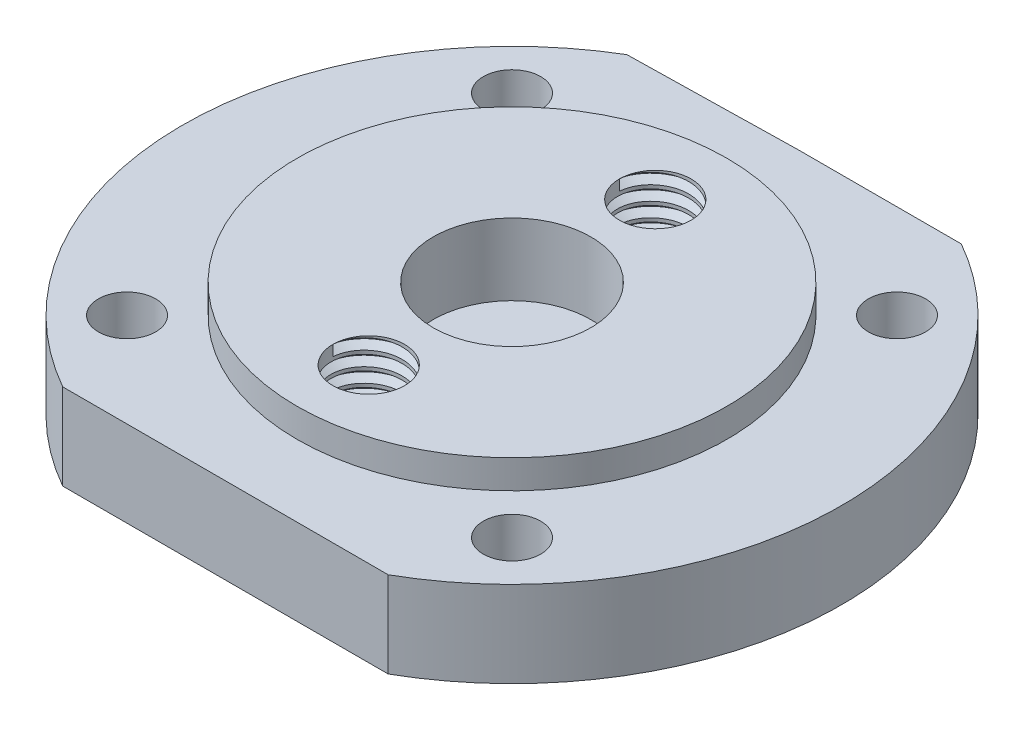
SolidWorks part; units mm, degrees
material "6061 Alloy"
ref_plane "Front Plane" through (0, 0, 0) normal (0, 0, 1) x (1, 0, 0)
ref_plane "Top Plane" through (0, 0, 0) normal (0, 1, 0) x (1, 0, 0)
ref_plane "Right Plane" through (0, 0, 0) normal (1, 0, 0) x (0, 0, -1)
sketch "Sketch1" plane through (0, 0, 0) normal (0, 1, 0) x (1, 0, 0)
  line L0 (0, 0) -> (0, 19.9983)
  line L1 (0, 0) -> (0, -20)
  line L2 (0, 19.9983) -> (11.3608, 19.9983)
  line L3 (0, 19.9983) -> (-11.7567, 19.7681)
  line L4 (0, -20) -> (-11.3578, -20)
  line L5 (0, -20) -> (11.3578, -20)
  circle A0 centre (0, 0) radius 23
  dimension "D1" = 46
  dimension "D2" = 19.9983
  dimension "D3" = 20
extrude "Boss-Extrude1" add sketch "Sketch1" along normal blind 6 contours L3 A0 L4 L1 L0 | L5 A0 L2 L0 L1
sketch "Sketch2" plane through (0, 6, 0) normal (0, 1, 0) x (1, 0, 0)
  line L0 (0, 0) -> (13.435, 13.435)
  line L1 (0, 0) -> (-13.435, -13.435)
  line L2 (13.435, 13.435) -> (-13.435, 13.435)
  line L3 (13.435, 13.435) -> (13.435, -13.435)
  line L4 (13.435, -13.435) -> (-13.435, -13.435)
  line L5 (-13.435, 13.435) -> (-13.435, -13.435)
  circle A0 centre (0, 0) radius 19
  circle A1 centre (-13.435, 13.435) radius 2
  circle A2 centre (13.435, 13.435) radius 2
  circle A3 centre (-13.435, -13.435) radius 2
  circle A4 centre (13.435, -13.435) radius 2
  dimension "D1" = 38
extrude "Cut-Extrude1" cut sketch "Sketch2" against normal through all contours L5 A1 L2 | A0 A1 L5 | L2 A1 A0 | A0 A1 | L4 A3 L1 | L1 A3 L5 | L5 A3 A0 | A0 A3 L4 | A0 A3 | L4 A4 A0 | L3 A4 L4 | A0 A4 L3 | A0 A4 | L0 A2 L3 | L2 A2 L0 | A0 A2 L2 | L3 A2 A0 | A0 A2
sketch "Sketch3" plane through (0, 6, 0) normal (0, 1, 0) x (1, 0, 0)
  circle A0 centre (0, 0) radius 15
extrude "Boss-Extrude2" add sketch "Sketch3" along normal blind 2
sketch "Sketch4" plane through (0, 8, 0) normal (0, 1, 0) x (1, 0, 0)
  circle A0 centre (0, 0) radius 5.5
extrude "Cut-Extrude2" cut sketch "Sketch4" against normal blind 5
sketch "Sketch5" plane through (0, 8, 0) normal (0, 1, 0) x (1, 0, 0)
  point P0 (0, 0)
  point P5 (0, 10)
  point P6 (0, -10)
hole_wizard "M6 Tapped Hole1" positions "Sketch13" profile "Sketch7" tap size "M6" standard "ISO" end condition through all
sketch "Sketch13" plane through (0, 8, 0) normal (0, 1, 0) x (1, 0, 0)
  point P0 (0, 10)
  point P3 (0, -10)
sketch "Sketch7" plane through (0, 8, -10) normal (1, 0, 0) x (0, 0, 1)
  line L0 (0, 0) -> (0, 8)
  line L1 (0, 8) -> (2.5, 8)
  line L2 (2.5, 8) -> (2.5, 0)
  line L5 (2.5, 0) -> (0, 0)
  line L11 (0, -6.35) -> (0, 107.95) construction
  dimension "Thru Tap Drill Dia." = 5
  dimension "Thru Tap Drill Depth" = 8
cosmetic thread "Hole Thread1" parameters "D2"=6
cosmetic thread "Hole Thread2" parameters "D2"=6
thread "Thread1" pitch 1 profile "Thread Profile1" start angle 0, offset 0, length 100, pitch 1, diameter 5
ref_plane "Plane1" through (-2.5, 8, -10) normal (0, 0, 1) x (-1, 0, 0)
sketch "Thread Profile1" plane through (-2.5, 8, -10) normal (0, 0, 1) x (-1, 0, 0)
  line L0 (0, 0) -> (0, 1) construction
  line L1 (0, 0) -> (0.5413, 0.3125)
  line L2 (0.5413, 0.3125) -> (0.5413, 0.4375)
  line L3 (0.5413, 0.4375) -> (0, 0.75)
  line L4 (0.5413, 0.375) -> (0, 0.375) construction
  line L11 (0, 0) -> (0, 0.75)
  point P2 (0, 0)
  dimension "Pitch" = 1
  dimension "Profile_Angle" = 60
  dimension "Profile_Land" = 0.125
  dimension "Profile_Height" = 0.5413
thread "Thread2" pitch 1 profile "Thread Profile2" start angle 0, offset 0, length 100, pitch 1, diameter 5
ref_plane "Plane2" through (-2.5, 8, 10) normal (0, 0, 1) x (-1, 0, 0)
sketch "Thread Profile2" plane through (-2.5, 8, 10) normal (0, 0, 1) x (-1, 0, 0)
  line L0 (0, 0) -> (0, 1) construction
  line L1 (0, 0) -> (0.5413, 0.3125)
  line L2 (0.5413, 0.3125) -> (0.5413, 0.4375)
  line L3 (0.5413, 0.4375) -> (0, 0.75)
  line L4 (0.5413, 0.375) -> (0, 0.375) construction
  line L11 (0, 0) -> (0, 0.75)
  point P2 (0, 0)
  dimension "Pitch" = 1
  dimension "Profile_Angle" = 60
  dimension "Profile_Land" = 0.125
  dimension "Profile_Height" = 0.5413
